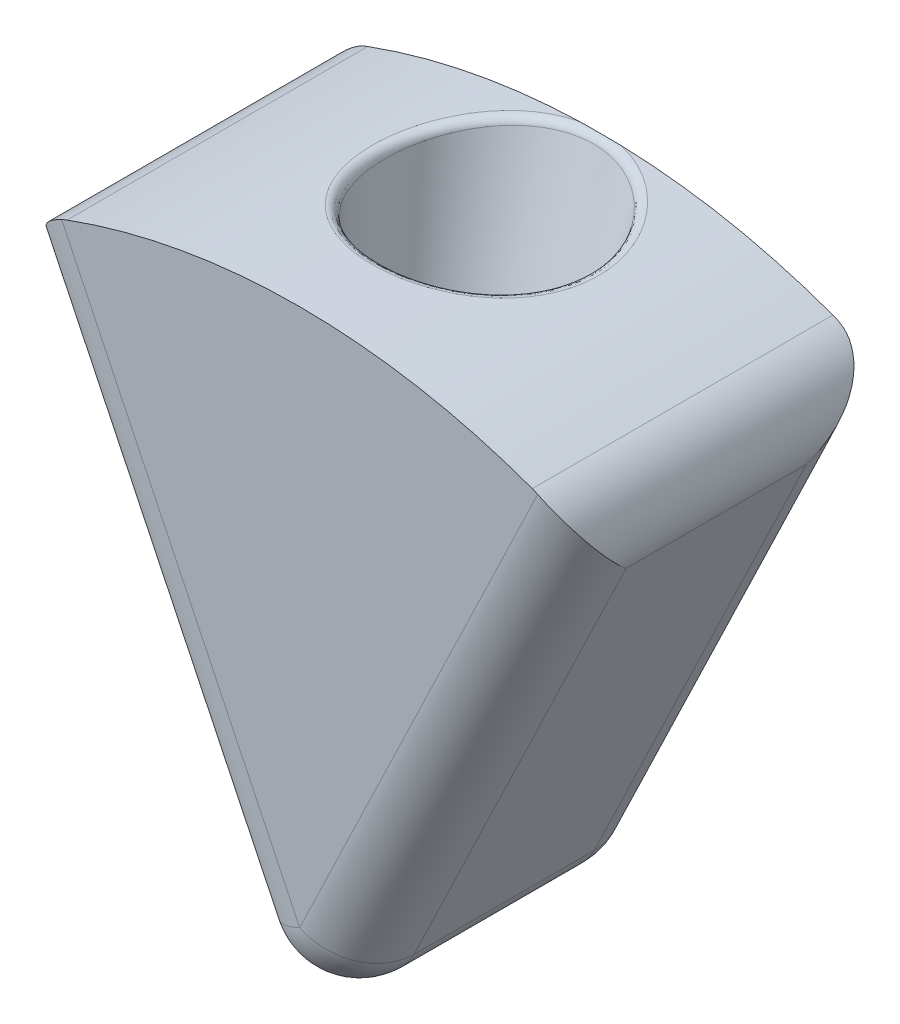
SolidWorks part; units mm, degrees
ref_plane "Front Plane" through (0, 0, 0) normal (1, 0, 0) x (0, 1, 0)
ref_plane "Top Plane" through (0, 0, 0) normal (0, 0, 1) x (0, 1, 0)
ref_plane "Right Plane" through (0, 0, 0) normal (0, 1, 0) x (-1, 0, 0)
sketch "Sketch1" plane through (0, 0, 0) normal (0, 0, 1) x (0, 1, 0)
  circle A0 centre (0, 0) radius 22.5
  dimension "D1" = 45
extrude "Boss-Extrude1" add sketch "Sketch1" along normal blind 10
sketch "Sketch8" plane through (0, 6.5, 0) normal (0, 1, 0) x (-1, 0, 0)
  circle A0 centre (0, 6.8449) radius 2.8
  point P3 (0, 7.5542)
  point P4 (0, 7.3546)
  point P5 (0, 6.8449)
  dimension "D1" = 5.6
sketch "Sketch10" plane through (0, 0, 10) normal (0, 0, 1) x (1, 0, 0)
  line L18 (0, 0) -> (-9.7624, 20.2718)
  line L19 (0, 0) -> (9.7624, 20.2718)
  circle A1 centre (0, 0) radius 22.5 construction
  arc A2 (-9.7624, 20.2718) -> (9.7624, 20.2718) centre (0, 0) ccw
extrude "Cut-Extrude1" cut sketch "Sketch10" against normal through all contours L19 A2 L18
sketch "Sketch11" plane through (0, 0, 10) normal (0, 0, 1) x (1, 0, 0)
  circle A0 centre (0, 0) radius 4.6028
sketch "Sketch14" plane through (0, 23.5, 0) normal (0, 1, 0) x (-1, 0, 0)
  line L0 (0, 10) -> (0, 0) construction
  line L1 (9.7624, 10) -> (-9.7624, 10) construction
  line L2 (-9.7624, 0) -> (9.7624, 0) construction
  circle A0 centre (0, 3.6086) radius 3.45
  dimension "D1" = 3.45
ref_axis "Axis2" through (0, 6.5196, 6.8412) along (0, 0.9824, -0.187)
ref_plane "Plane6" through (0, 0, 0) normal (1, 0, 0) x (0, 0.9824, -0.187)
sketch "Sketch15" plane through (0, 0, 0) normal (1, 0, 0) x (0, 0.9824, -0.187)
  line L1 (22.4106, 7.9397) -> (22.4039, 11.5697)
  line L8 (5.1052, 7.9397) -> (5.1052, 9.2179)
  line L9 (5.6289, 5.1891) -> (4.5816, 10.6903) construction
  line L10 (5.1052, 9.2179) -> (22.4039, 11.5697)
  line L11 (22.4106, 7.9397) -> (5.1052, 7.9397)
  dimension "D3" = 3.63
revolve "Cut-Revolve3" cut sketch "Sketch15" angle 360 about L11
fillet "Fillet1" radius 2 7 edges at (9.7624, 20.2718, 5) (4.8812, 10.1359, 0) (4.8812, 10.1359, 10) (0, 0, 5) (-4.8812, 10.1359, 0) (-9.7624, 20.2718, 5) (-4.8812, 10.1359, 10)
fillet "Fillet3" radius 0.3 2 edges at (2.0374, 22.4076, 6.5988) (0, 6.739, 8.1006)
